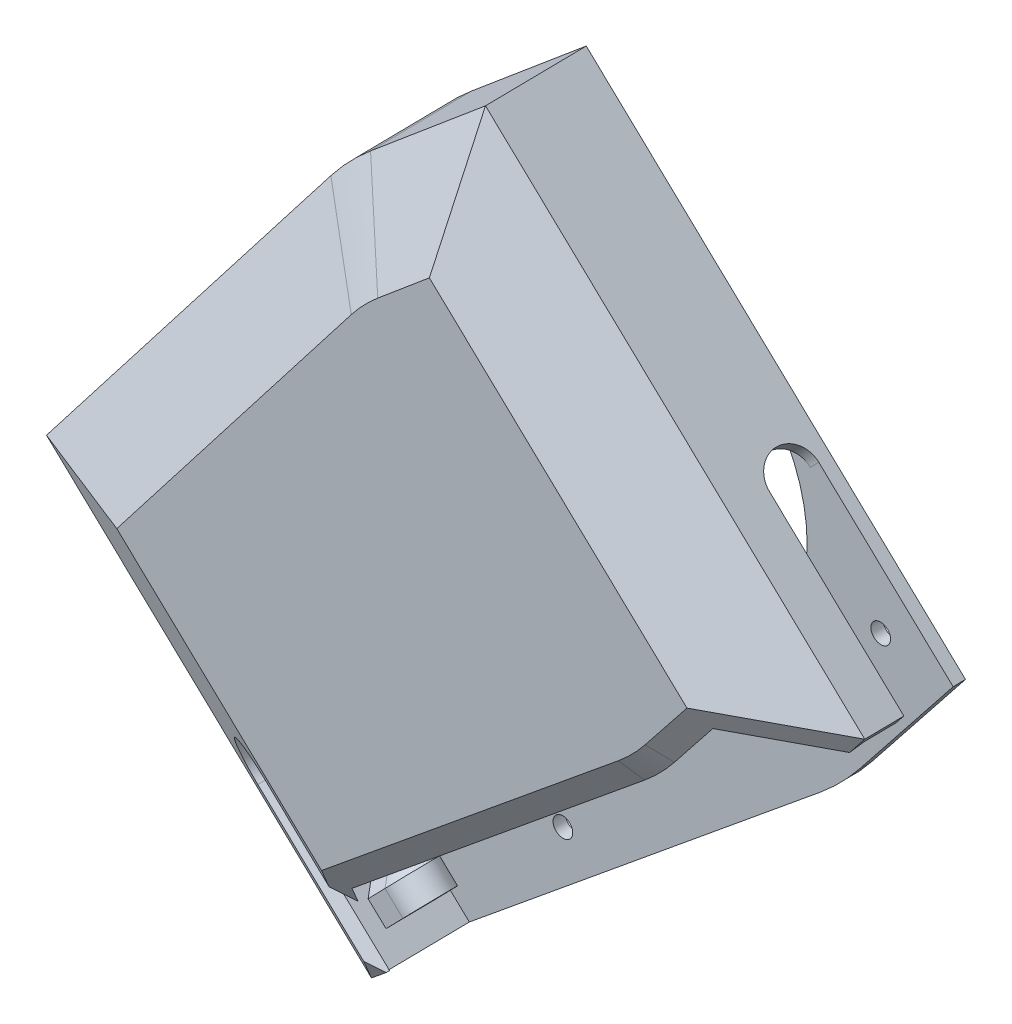
SolidWorks part; units mm, degrees
material "ABS"
ref_plane "Front Plane" through (0, 0, 0) normal (0, 0, 1) x (1, 0, 0)
ref_plane "Top Plane" through (0, 0, 0) normal (0, 1, 0) x (1, 0, 0)
ref_plane "Right Plane" through (0, 0, 0) normal (1, 0, 0) x (0, 0, -1)
sketch "Sketch1" plane through (0, 1.5399, -108.8354) normal (0, -0.0141, 0.9999) x (1, 0, 0)
  line L0 (-63.9977, 99.1574) -> (-31.4443, 126.5628) construction
  line L1 (-138.5132, 4.9856) -> (-70.5336, 92.3642) construction
  line L2 (-6.4305, 29.9782) -> (-91.9316, -40.3482) construction
  line L3 (77.4087, 133.6531) -> (0.1827, 36.6962) construction
  line L4 (-63.9977, 99.1574) -> (-45.1299, 115.0415)
  line L5 (-117.5072, 31.9859) -> (-70.5336, 92.3642)
  line L6 (-6.4305, 29.9782) -> (-65.5114, -18.6171)
  line L7 (15.5488, 55.9882) -> (0.1827, 36.6962)
  line L8 (15.5488, 55.9882) -> (-45.1299, 115.0415)
  line L9 (-65.5114, -18.6171) -> (-117.5072, 31.9859)
  line L10 (-91.9316, -40.3482) -> (-138.5132, 4.9856) construction
  line L12 (12.7718, 58.6908) -> (5.2933, 65.969) construction
  arc A0 (-63.9977, 99.1574) -> (-70.5336, 92.3642) centre (-35.0164, 64.7323) ccw construction
  arc A1 (-6.4305, 29.9782) -> (0.1827, 36.6962) centre (-35.0164, 64.7323) ccw construction
  arc A2 (-63.9977, 99.1574) -> (-70.5336, 92.3642) centre (-35.0164, 64.7323) ccw
  arc A3 (-6.4305, 29.9782) -> (0.1827, 36.6962) centre (-35.0164, 64.7323) ccw
  dimension "D1" = 110
extrude "Extrude1" add sketch "Sketch1" along normal blind 25 contours L4 L8 L7 A3 L6 L9 L5 A2
chamfer "Chamfer1" distance 15 angle 30 8 edges at (-14.7906, 86.6925, -82.628) (7.8658, 47.5238, -83.1822) (-54.5638, 108.2749, -82.3227) (-2.9475, 34.3465, -83.3687) (-67.444, 97.109, -82.4807) (-35.9709, 6.8662, -83.7575) (-91.5093, 7.87, -83.7433) (-94.0204, 63.3551, -82.9582) first distance on face at (-44.1726, 56.5047, -83.0552)
ref_plane "Plane1" through (-24.3398, 23.6854, 0.3351) normal (-0.7166, 0.6974, 0.0099) x (0, 0.0141, -0.9999)
sketch "Sketch3" plane through (-26.3027, 21.6687, 0.3066) normal (0.7166, -0.6974, -0.0099) x (-0.0077, 0.0062, -1)
  line L0 (106.2666, 52.9614) -> (107.4397, -53.0321)
  line L1 (107.4397, -53.0321) -> (94.2555, -53.178)
  line L2 (94.2555, -53.178) -> (86.2912, -39.7294)
  line L3 (86.2912, -39.7294) -> (85.4177, 39.194)
  line L4 (85.4177, 39.194) -> (93.0824, 52.8155)
  line L5 (93.0824, 52.8155) -> (106.2666, 52.9614)
  line L6 (91.9056, 54.8026) -> (108.2444, 54.9835) construction
  line L7 (107.151, 153.779) -> (108.516, 30.4426) construction
  line L10 (84.2973, -40.2874) -> (93.123, -55.1906) construction
  line L11 (84.2973, -40.2874) -> (83.6035, 22.3961) construction
  line L12 (91.9056, 54.8026) -> (83.4119, 39.7077) construction
  line L13 (83.534, 28.6801) -> (83.4119, 39.7077) construction
  line L15 (93.123, -55.1906) -> (109.4617, -55.0098) construction
  line L16 (108.6203, 21.0165) -> (109.4617, -55.0098) construction
  dimension "D1" = 2
  dimension "D2" = 2
  dimension "D3" = 2
  dimension "D4" = 2
  dimension "D5" = 2
  dimension "D6" = 2
extrude "Cut-Extrude2" cut sketch "Sketch3" against normal blind 15 and the other way blind 15
shell "Shell1" thickness 2 removed face at (-37.9016, 32.607, -94.9994)
sketch "Sketch5" plane through (0, 1.5116, -106.8356) normal (0, -0.0141, 0.9999) x (1, 0, 0)
  circle A0 centre (-35.0164, 64.7323) radius 27
  dimension "D1" = 54
extrude "Cut-Extrude3" cut sketch "Sketch5" against normal blind 15
sketch "Sketch6" plane through (17.6442, 18.748, -43.5573) normal (-0.3487, -0.3705, 0.8609) x (0.9372, -0.1379, 0.3203)
  line L0 (-102.7872, -29.3525) -> (-81.1427, -47.5951) construction
  line L1 (-98.9204, -24.7647) -> (-77.276, -43.0072)
  line L2 (-106.654, -33.9403) -> (-85.0095, -52.1829)
  line L3 (-88.7252, -52.5698) -> (-144.2036, -5.8111) construction
  line L4 (-87.8287, -30.6735) -> (-88.7252, -52.5698) construction
  arc A0 (-98.9204, -24.7647) -> (-106.654, -33.9403) centre (-102.7872, -29.3525) ccw
  arc A1 (-85.0095, -52.1829) -> (-77.276, -43.0072) centre (-81.1427, -47.5951) ccw
  point P2 (-91.965, -38.4738)
  dimension "D1" = 6
  dimension "D2" = 15
extrude "Cut-Extrude4" cut sketch "Sketch6" against normal blind 5
sketch "Sketch7" plane through (35.5471, 36.5219, 0.5167) normal (0.6974, 0.7166, 0.0101) x (0.7166, -0.6974, -0.0099)
  line L0 (-20.9692, 102.8462) -> (-57.9057, 102.8462) construction
  line L1 (-20.9692, 98.8462) -> (-57.9057, 98.8462)
  line L2 (-20.9692, 106.8462) -> (-57.9057, 106.8462)
  line L3 (-27.7066, 106.8462) -> (-70.2412, 106.8462) construction
  line L4 (-27.9057, 92.5065) -> (-27.9057, 108.8462) construction
  arc A0 (-20.9692, 98.8462) -> (-20.9692, 106.8462) centre (-20.9692, 102.8462) ccw
  arc A1 (-57.9057, 106.8462) -> (-57.9057, 98.8462) centre (-57.9057, 102.8462) ccw
  point P2 (-39.4375, 102.8462)
  dimension "D1" = 4
  dimension "D2" = 30
extrude "Cut-Extrude5" cut sketch "Sketch7" against normal blind 5
sketch "Sketch8" plane through (0, 1.5116, -106.8356) normal (0, -0.0141, 0.9999) x (1, 0, 0)
  line L0 (-95.4785, 49.6185) -> (-48.4904, 3.8891) construction
  line L1 (-95.4785, 49.6185) -> (-43.1702, 103.3665) construction
  line L2 (-48.4904, 3.8891) -> (3.8178, 57.6371) construction
  line L3 (-43.1702, 103.3665) -> (3.8178, 57.6371) construction
  line L4 (-63.9573, -17.3388) -> (-114.8295, 32.1707) construction
  line L5 (-16.1854, 84.0816) -> (-45.2271, 112.3453) construction
  circle A0 centre (-95.4785, 49.6185) radius 1.6
  circle A1 centre (-48.4904, 3.8891) radius 1.6
  circle A2 centre (-43.1702, 103.3665) radius 1.6
  circle A3 centre (3.8178, 57.6371) radius 1.6
  dimension "D5" = 3.2
  dimension "D1" = 5
  dimension "D2" = 75
  dimension "D3" = 12
  dimension "D4" = 10
extrude "Cut-Extrude6" cut sketch "Sketch8" against normal blind 5
ref_plane "Plane2" through (-24.3398, 23.6854, 0.3351) normal (-0.7166, 0.6974, 0.0099) x (0, 0.0141, -0.9999)
ref_plane "Plane3" through (-27.2063, 26.4749, 0.3746) normal (-0.7166, 0.6974, 0.0099) x (0, 0.0141, -0.9999)
sketch "Sketch9" plane through (-27.2063, 26.4749, 0.3746) normal (-0.7166, 0.6974, 0.0099) x (0, 0.0141, -0.9999)
  line L0 (104.3937, 57.0322) -> (96.3937, 57.0322)
  line L1 (104.3937, 57.0322) -> (104.3937, 53.0322)
  line L2 (96.3937, 57.0322) -> (96.3937, 53.0322)
  line L4 (106.8462, 57.0322) -> (93.6612, 57.0322) construction
  line L6 (96.813, -49.9209) -> (99.048, -46.9707)
  line L7 (90.5858, -44.8927) -> (92.6713, -42.1399)
  line L9 (96.813, -49.9209) -> (93.2029, -49.9209)
  line L10 (93.2029, -49.9209) -> (90.5858, -44.8927)
  arc A0 (104.3937, 53.0322) -> (96.3937, 53.0322) centre (100.3937, 53.0322) cw
  arc A1 (99.048, -46.9707) -> (92.6713, -42.1399) centre (95.8596, -44.5553) ccw
  circle A2 centre (100.3937, 53.0322) radius 1.3
  circle A3 centre (95.8596, -44.5553) radius 1.3
  circle A4 centre (95.8596, -44.5553) radius 3 construction
  dimension "D1" = 2.6
  dimension "D2" = 4
  dimension "D4" = 6
  dimension "D3" = 4
extrude "Extrude2" add sketch "Sketch9" along normal blind 8
chamfer "Chamfer2" distance 4 angle 45 6 edges at (-71.3213, -5.9036, -104.4877) (-67.1366, -1.6607, -100.4273) (-71.3213, -6.0167, -96.4885) (0.5164, 67.8177, -97.3418) (-4.0884, 63.0865, -97.3923) (-2.7781, 64.3415, -90.9324)
